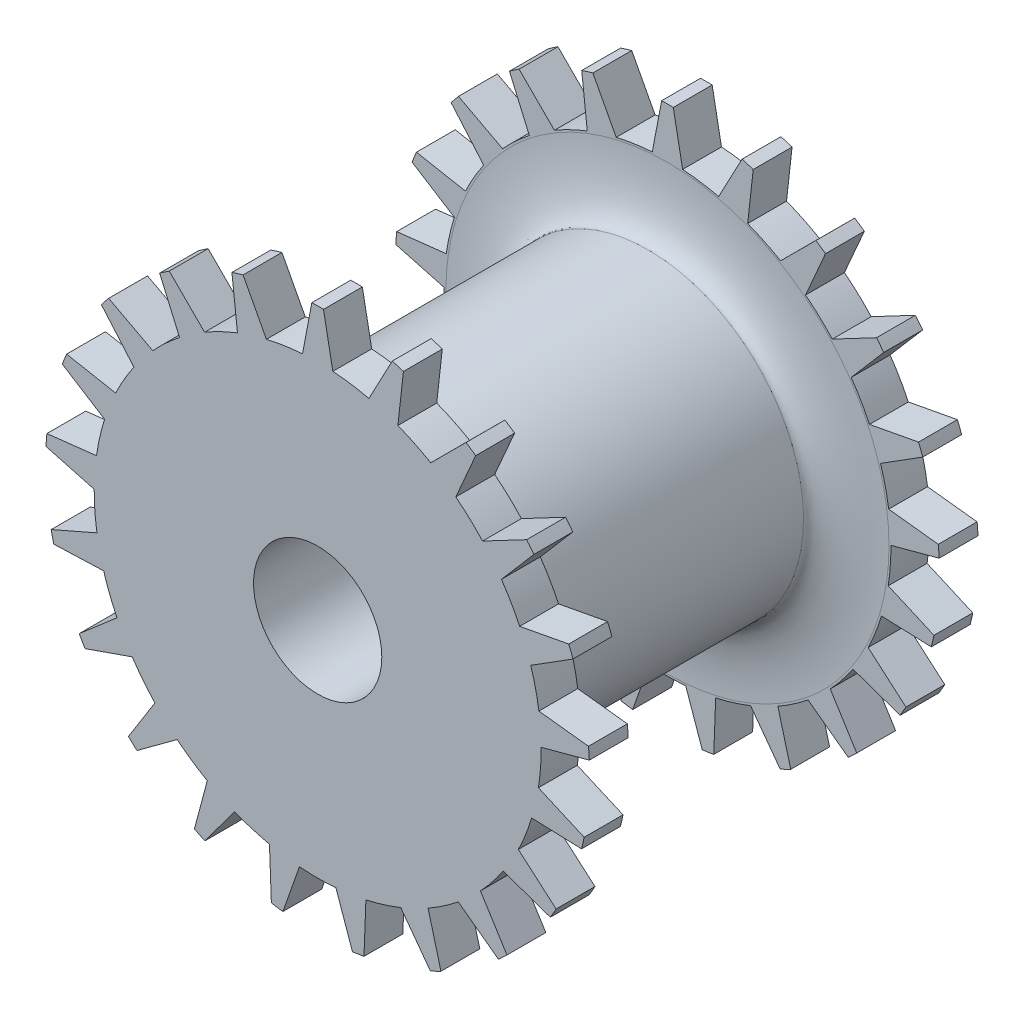
SolidWorks part; units mm, degrees
ref_plane "Front" through (0, 0, 0) normal (0, 0, 1) x (1, 0, 0)
ref_plane "Top" through (0, 0, 0) normal (0, 1, 0) x (1, 0, 0)
ref_plane "Right" through (0, 0, 0) normal (1, 0, 0) x (0, 0, -1)
sketch "草图1" plane through (0, 0, 0) normal (0, 0, 1) x (1, 0, 0)
  line L0 (-0.15, 6.9984) -> (-0.39, 5.7368)
  line L1 (0.15, 6.9984) -> (0.3898, 5.7368)
  line L2 (2.2061, 6.6433) -> (2.0634, 5.367)
  line L3 (1.9195, 6.7317) -> (1.3183, 5.5968)
  line L4 (4.0663, 5.6978) -> (3.5537, 4.5204)
  line L5 (3.8184, 5.8668) -> (2.9094, 4.9596)
  line L6 (5.5651, 4.2462) -> (4.7282, 3.2721)
  line L7 (5.378, 4.4807) -> (4.242, 3.8817)
  line L8 (6.5694, 2.4172) -> (5.4826, 1.733)
  line L9 (6.4598, 2.6964) -> (5.1977, 2.4589)
  line L10 (6.99, 0.3734) -> (5.7499, 0.04)
  line L11 (6.9676, 0.6726) -> (5.6916, 0.8176)
  line L12 (6.7896, -1.7035) -> (5.5062, -1.6566)
  line L13 (6.8563, -1.411) -> (5.6797, -0.8963)
  line L14 (5.9858, -3.6291) -> (4.7733, -3.2059)
  line L15 (6.1358, -3.3693) -> (5.1632, -2.5306)
  line L16 (4.6502, -5.2322) -> (3.6163, -4.4705)
  line L17 (4.8701, -5.0282) -> (4.1879, -3.9401)
  line L18 (2.9013, -6.3704) -> (2.1379, -5.3378)
  line L19 (3.1716, -6.2403) -> (2.8405, -4.9994)
  line L20 (0.8947, -6.9426) -> (0.4696, -5.7308)
  line L21 (1.1914, -6.8979) -> (1.2407, -5.6146)
  line L22 (-1.1914, -6.8979) -> (-1.2404, -5.6146)
  line L23 (-0.8947, -6.9426) -> (-0.4694, -5.7308)
  line L24 (-3.1716, -6.2403) -> (-2.8403, -4.9995)
  line L25 (-2.9013, -6.3704) -> (-2.1377, -5.3379)
  line L26 (-4.8701, -5.0282) -> (-4.1877, -3.9402)
  line L27 (-4.6502, -5.2322) -> (-3.6161, -4.4706)
  line L28 (-6.1358, -3.3693) -> (-5.1631, -2.5308)
  line L29 (-5.9858, -3.6291) -> (-4.7732, -3.2061)
  line L30 (-6.8563, -1.411) -> (-5.6797, -0.8965)
  line L31 (-6.7896, -1.7035) -> (-5.5061, -1.6568)
  line L32 (-6.9676, 0.6726) -> (-5.6916, 0.8174)
  line L33 (-6.99, 0.3734) -> (-5.7499, 0.0398)
  line L34 (-6.4598, 2.6964) -> (-5.1978, 2.4587)
  line L35 (-6.5694, 2.4172) -> (-5.4827, 1.7328)
  line L36 (-5.378, 4.4807) -> (-4.2422, 3.8816)
  line L37 (-5.5651, 4.2462) -> (-4.7283, 3.2719)
  line L38 (-3.8184, 5.8668) -> (-2.9096, 4.9595)
  line L39 (-4.0663, 5.6978) -> (-3.5539, 4.5202)
  line L40 (-1.9195, 6.7317) -> (-1.3185, 5.5968)
  line L41 (-2.2061, 6.6433) -> (-2.0636, 5.3669)
  arc A0 (-0.39, 5.7368) -> (-1.3185, 5.5968) centre (0, 0) ccw
  arc A2 (0.15, 6.9984) -> (-0.15, 6.9984) centre (0, 0) ccw
  arc A3 (2.2061, 6.6433) -> (1.9195, 6.7317) centre (0, 0) ccw
  arc A4 (4.0663, 5.6978) -> (3.8184, 5.8668) centre (0, 0) ccw
  arc A5 (5.5651, 4.2462) -> (5.378, 4.4807) centre (0, 0) ccw
  arc A6 (6.5694, 2.4172) -> (6.4598, 2.6964) centre (0, 0) ccw
  arc A7 (6.99, 0.3734) -> (6.9676, 0.6726) centre (0, 0) ccw
  arc A8 (6.7896, -1.7035) -> (6.8563, -1.411) centre (0, 0) ccw
  arc A9 (5.9858, -3.6291) -> (6.1358, -3.3693) centre (0, 0) ccw
  arc A10 (4.6502, -5.2322) -> (4.8701, -5.0282) centre (0, 0) ccw
  arc A11 (2.9013, -6.3704) -> (3.1716, -6.2403) centre (0, 0) ccw
  arc A12 (0.8947, -6.9426) -> (1.1914, -6.8979) centre (0, 0) ccw
  arc A13 (-1.1914, -6.8979) -> (-0.8947, -6.9426) centre (0, 0) ccw
  arc A14 (-3.1716, -6.2403) -> (-2.9013, -6.3704) centre (0, 0) ccw
  arc A15 (-4.8701, -5.0282) -> (-4.6502, -5.2322) centre (0, 0) ccw
  arc A16 (-6.1358, -3.3693) -> (-5.9858, -3.6291) centre (0, 0) ccw
  arc A17 (-6.8563, -1.411) -> (-6.7896, -1.7035) centre (0, 0) ccw
  arc A18 (-6.9676, 0.6726) -> (-6.99, 0.3734) centre (0, 0) ccw
  arc A19 (-6.4598, 2.6964) -> (-6.5694, 2.4172) centre (0, 0) ccw
  arc A20 (-5.378, 4.4807) -> (-5.5651, 4.2462) centre (0, 0) ccw
  arc A21 (-3.8184, 5.8668) -> (-4.0663, 5.6978) centre (0, 0) ccw
  arc A22 (-1.9195, 6.7317) -> (-2.2061, 6.6433) centre (0, 0) ccw
  arc A23 (-2.0636, 5.3669) -> (-2.9096, 4.9595) centre (0, 0) ccw
  arc A24 (-3.5539, 4.5202) -> (-4.2422, 3.8816) centre (0, 0) ccw
  arc A25 (1.3183, 5.5968) -> (0.3898, 5.7368) centre (0, 0) ccw
  arc A26 (2.9094, 4.9596) -> (2.0634, 5.367) centre (0, 0) ccw
  arc A27 (4.242, 3.8817) -> (3.5537, 4.5204) centre (0, 0) ccw
  arc A28 (-4.7283, 3.2719) -> (-5.1978, 2.4587) centre (0, 0) ccw
  arc A29 (-5.4827, 1.7328) -> (-5.6916, 0.8174) centre (0, 0) ccw
  arc A30 (-5.7499, 0.0398) -> (-5.6797, -0.8965) centre (0, 0) ccw
  arc A31 (-5.5061, -1.6568) -> (-5.1631, -2.5308) centre (0, 0) ccw
  arc A32 (-4.7732, -3.2061) -> (-4.1877, -3.9402) centre (0, 0) ccw
  arc A33 (-3.6161, -4.4706) -> (-2.8403, -4.9995) centre (0, 0) ccw
  arc A34 (-2.1377, -5.3379) -> (-1.2404, -5.6146) centre (0, 0) ccw
  arc A35 (-0.4694, -5.7308) -> (0.4696, -5.7308) centre (0, 0) ccw
  arc A36 (1.2407, -5.6146) -> (2.1379, -5.3378) centre (0, 0) ccw
  arc A37 (2.8405, -4.9994) -> (3.6163, -4.4705) centre (0, 0) ccw
  arc A38 (4.1879, -3.9401) -> (4.7733, -3.2059) centre (0, 0) ccw
  arc A39 (5.1632, -2.5306) -> (5.5062, -1.6566) centre (0, 0) ccw
  arc A40 (5.6797, -0.8963) -> (5.7499, 0.04) centre (0, 0) ccw
  arc A41 (5.6916, 0.8176) -> (5.4826, 1.733) centre (0, 0) ccw
  arc A42 (5.1977, 2.4589) -> (4.7282, 3.2721) centre (0, 0) ccw
  point P3 (0, 5.75)
  point P5 (0, 7)
  point P6 (-0.39, 5.7368)
  point P7 (0.3898, 5.7368)
  point P8 (-0.15, 6.9984)
  point P9 (0.15, 6.9984)
  point P95 (0, 0)
  dimension "D1" = 0.39
  dimension "D5" = 11.5
  dimension "D6" = 14
  dimension "D7" = 21
  dimension "D2" = 0.39
  dimension "D3" = 0.15
  dimension "D4" = 0.15
extrude "凸台-拉伸1" add sketch "草图1" along normal mid plane 10
sketch "草图2" plane through (0, 0, 0) normal (0, 0, 1) x (1, 0, 0)
  circle A0 centre (0, 0) radius 1.65
  dimension "D1" = 3.3
extrude "切除-拉伸1" cut sketch "草图2" against normal through all both and the other way through all
sketch "草图3" plane through (0, 0, 0) normal (0, 0, 1) x (1, 0, 0)
  circle A0 centre (0, 0) radius 3
  dimension "D1" = 6
extrude "切除-拉伸2" cut sketch "草图3" against normal through all
sketch "草图4" plane through (0, 0, 0) normal (0, 0, 1) x (1, 0, 0)
  circle A0 centre (0, 0) radius 3
  dimension "D1" = 6
extrude "切除-拉伸3" cut sketch "草图4" along normal blind 2
sketch "草图5" plane through (0, 0, 0) normal (0, 0, 1) x (1, 0, 0)
  circle A0 centre (0, 0) radius 5
  circle A1 centre (0, 0) radius 7.8194
  dimension "D1" = 10
extrude "切除-拉伸4" cut sketch "草图5" against normal mid plane 8
sketch "草图6" plane through (0, 0, 0) normal (0, 0, 1) x (1, 0, 0)
  circle A0 centre (0, 0) radius 4
  circle A1 centre (0, 0) radius 8.2316
  dimension "D1" = 8
extrude "切除-拉伸5" cut sketch "草图6" along normal blind 4
sketch "草图7" plane through (0, 0, 0) normal (0, 0, 1) x (1, 0, 0)
  circle A0 centre (0, 0) radius 4
  circle A1 centre (0, 0) radius 7.4674
  dimension "D1" = 8
extrude "切除-拉伸6" cut sketch "草图7" against normal blind 4
fillet "圆角1" radius 0.5 1 edges at (4, 0, 4) second distance 1.7 first distance on face at (4, 0, 4)
fillet "圆角2" radius 1.7 1 edges at (4, 0, -4) second distance 0.5 first distance on face at (0, 0, -4)
